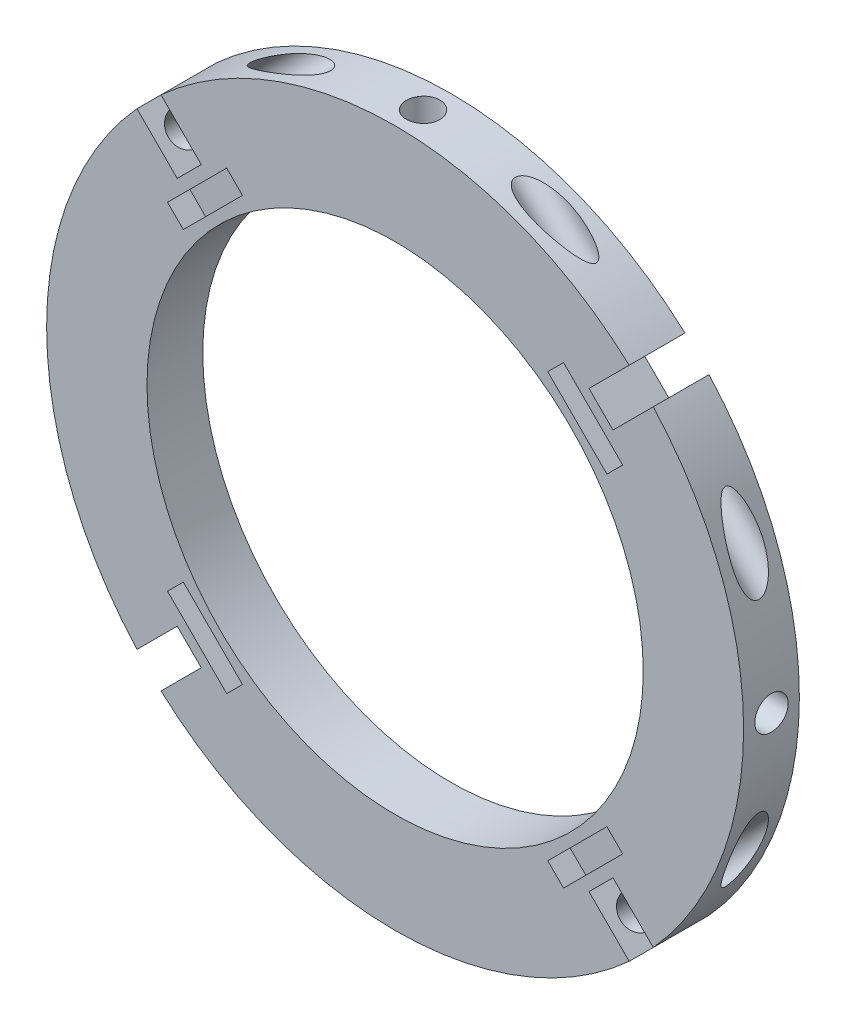
SolidWorks part; units mm, degrees
ref_plane "Ön Düzlem" through (0, 0, 0) normal (0, 0, 1) x (1, 0, 0)
ref_plane "Üst Düzlem" through (0, 0, 0) normal (0, 1, 0) x (1, 0, 0)
ref_plane "Sağ Düzlem" through (0, 0, 0) normal (1, 0, 0) x (0, 0, -1)
sketch "Sketch2" plane through (0, 0, 0) normal (0, 0, 1) x (1, 0, 0)
  circle A0 centre (0, 0) radius 62.5
  circle A1 centre (0, 0) radius 44.5
  dimension "D1" = 125
  dimension "D2" = 89
extrude "Boss-Extrude2" add sketch "Sketch2" along normal mid plane 10
sketch "Sketch3" plane through (0, 0, 5) normal (0, 0, 1) x (1, 0, 0)
  line L0 (0, 0) -> (44.1942, 44.1942) construction
  line L1 (34.601, 52.0483) -> (21.5092, 38.9565)
  line L2 (51.7927, 34.9824) -> (38.7281, 21.9178)
  line L3 (41.9884, 46.295) -> (34.7695, 39.0761)
  line L4 (34.7695, 39.0761) -> (39.0761, 34.7695)
  line L5 (39.0761, 34.7695) -> (46.295, 41.9884)
  line L6 (0, 0) -> (0, 62.5) construction
  line L7 (30.2053, 40.8119) -> (27.3769, 37.9835)
  line L8 (27.3769, 37.9835) -> (37.9835, 27.3769)
  line L9 (37.9835, 27.3769) -> (40.8119, 30.2053)
  line L10 (40.8119, 30.2053) -> (30.2053, 40.8119)
  line L11 (34.7695, 39.0761) -> (28.1992, 45.6464) construction
  circle A0 centre (0, 0) radius 62.5
  circle A1 centre (0, 0) radius 44.5
  point P17 (35.5086, 35.5086)
  point P19 (36.9228, 36.9228)
  point P20 (32.6802, 32.6802)
  point P21 (0, 0)
  point P22 (0, 0)
  circle M8 centre (0, 0) radius 62.5
  dimension "D1" = 125
  dimension "D2" = 89
  dimension "D3" = 45
  dimension "D4" = 4
  dimension "D5" = 15
  dimension "D6" = 4
extrude "Cut-Extrude1" cut sketch "Sketch3" against normal up to surface (10 mm away) contours L4 L5 L3 M8 region at (40.5498, 40.5498, 5) up to face at (62.5, 0, -5)
pattern_circular "CirPattern3" count 4 over 360 about axis through (0, 0, 5) along (0, 0, -1) of "Cut-Extrude1"
extrude "Cut-Extrude2" cut sketch "Sketch3<3>" against normal blind 4 contours L9 L10 L7 L8 region at (34.0944, 34.0944, 5)
sketch "Sketch3<3>" plane through (0, 0, 5) normal (0, 0, 1) x (1, 0, 0) same geometry as "Sketch3"
pattern_circular "CirPattern4" count 4 over 360 about axis through (0, 0, 5) along (0, 0, -1) of "Cut-Extrude2" reverse direction yes
sketch "Sketch4" plane through (-2.1533, 2.1533, 0) normal (0.7071, -0.7071, 0) x (0, 0, -1)
  line L0 (-5, 52.2167) -> (-5, 62.4258) construction
  line L1 (5, 52.2167) -> (5, 62.4258) construction
  line L2 (5, 57.3212) -> (-5, 57.3212) construction
  circle A0 centre (0, 57.3212) radius 3
  dimension "D1" = 6
extrude "Cut-Extrude3" cut sketch "Sketch4" against normal mid plane 126
pattern_circular "CirPattern5" count 4 over 360 about axis through (0, 0, 5) along (0, 0, -1) of "Cut-Extrude3"
sketch "Sketch5" plane through (0, 0, 0) normal (0, 1, 0) x (1, 0, 0)
  circle A0 centre (0, 0) radius 3
  dimension "D1" = 6
extrude "Cut-Extrude4" cut sketch "Sketch5" along normal blind 8 from offset 55
pattern_circular "CirPattern6" count 4 over 360 about axis through (0, 0, 5) along (0, 0, -1) of "Cut-Extrude4"
